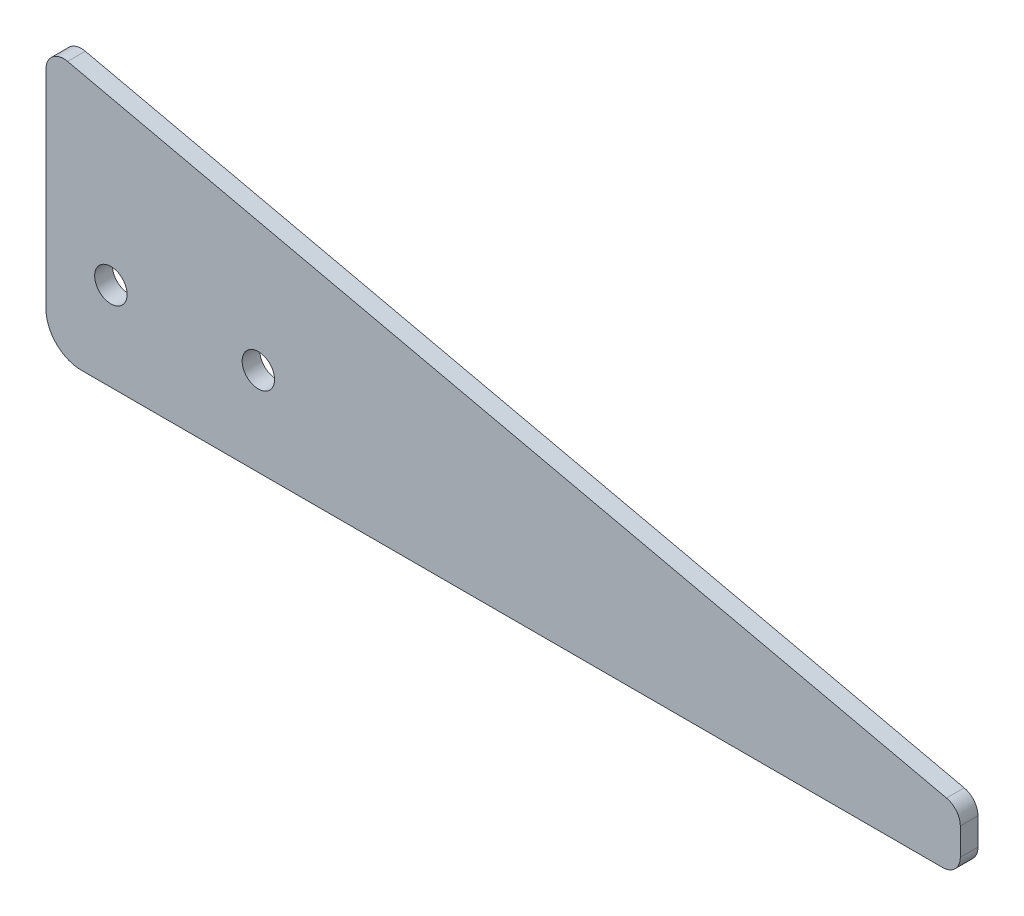
SolidWorks part; units mm, degrees
ref_plane "Front Plane" through (0, 0, 0) normal (0, 0, 1) x (1, 0, 0)
ref_plane "Top Plane" through (0, 0, 0) normal (0, 1, 0) x (1, 0, 0)
ref_plane "Right Plane" through (0, 0, 0) normal (1, 0, 0) x (0, 0, -1)
sketch "Sketch1" plane through (0, 0, 0) normal (0, 0, 1) x (1, 0, 0)
  line L0 (6, 0) -> (152, 0)
  line L1 (155, 3) -> (155, 7.6019)
  line L2 (152.6608, 10.5282) -> (3.6608, 44.1734)
  line L3 (0, 41.247) -> (0, 6)
  arc A0 (0, 6) -> (6, 0) centre (6, 6) ccw
  arc A1 (3.6608, 44.1734) -> (0, 41.247) centre (3, 41.247) ccw
  arc A2 (155, 7.6019) -> (152.6608, 10.5282) centre (152, 7.6019) ccw
  arc A3 (152, 0) -> (155, 3) centre (152, 3) ccw
  point P7 (0, 0)
  point P10 (0, 45)
  point P13 (155, 10)
  point P16 (155, 0)
  dimension "D4" = 6
  dimension "D5" = 3
  dimension "D6" = 3
  dimension "D1" = 155
  dimension "D2" = 10
  dimension "D3" = 45
base flange "Base-Flange1" sketch "Sketch1" thickness 3 reverse thickness direction no parameters "D1"=0.7366
sketch "Sketch6" plane through (0, 0, -3) normal (0, 0, -1) x (-1, 0, 0)
  line L0 (-6, 0) -> (-152, 0) construction
  line L1 (0, 41.247) -> (0, 6) construction
  circle A0 centre (-11, 15) radius 2.75
  circle A1 centre (-36, 15) radius 2.75
  dimension "D1" = 15
  dimension "D5" = 5.5
  dimension "D2" = 15
  dimension "D3" = 25
  dimension "D4" = 11
extrude "Cut-Extrude1" cut sketch "Sketch6" against normal blind 10 normal cut yes
sketch "Bend-Lines1" [suppressed] plane through (0, 0, 0) normal (0, 1, 0) x (1, 0, 0)
sketch "Bounding-Box1" [suppressed] plane through (0, 0, 0) normal (0, 1, 0) x (1, 0, 0)
sheet metal parameters "Sheet-Metal1" thickness 3 parameters "D1"=0.7366
flat pattern "Flat-Pattern1" [suppressed]
sketch "Bend-Lines2" plane through (0, 0, 0) normal (0, 1, 0) x (1, 0, 0)
sketch3d "Bounding-Box2" [suppressed]
  line L0 (-4.9965, 38.6946, 0) -> (111.0741, 3.3688, 0) construction
  line L1 (-17.0981, -1.0678, 0) -> (98.9725, -36.3936, 0) construction
  line L2 (-4.9965, 38.6946, 0) -> (-17.0981, -1.0678, 0) construction
  line L3 (111.0741, 3.3688, 0) -> (98.9725, -36.3936, 0) construction
sheet metal parameters "Sheet-Metal2" thickness 3 parameters "D1"=0.7366
flat pattern "Flat-Pattern1"
sketch "Bend-Lines2" plane through (0, 0, 0) normal (0, 1, 0) x (1, 0, 0)
sketch3d "Bounding-Box2" [suppressed]
  line L0 (-5.2655, 38.8342, 0) -> (150.5755, 3.6442, 0) construction
  line L1 (-14.6752, -2.8373, 0) -> (141.1658, -38.0272, 0) construction
  line L2 (-5.2655, 38.8342, 0) -> (-14.6752, -2.8373, 0) construction
  line L3 (150.5755, 3.6442, 0) -> (141.1658, -38.0272, 0) construction
